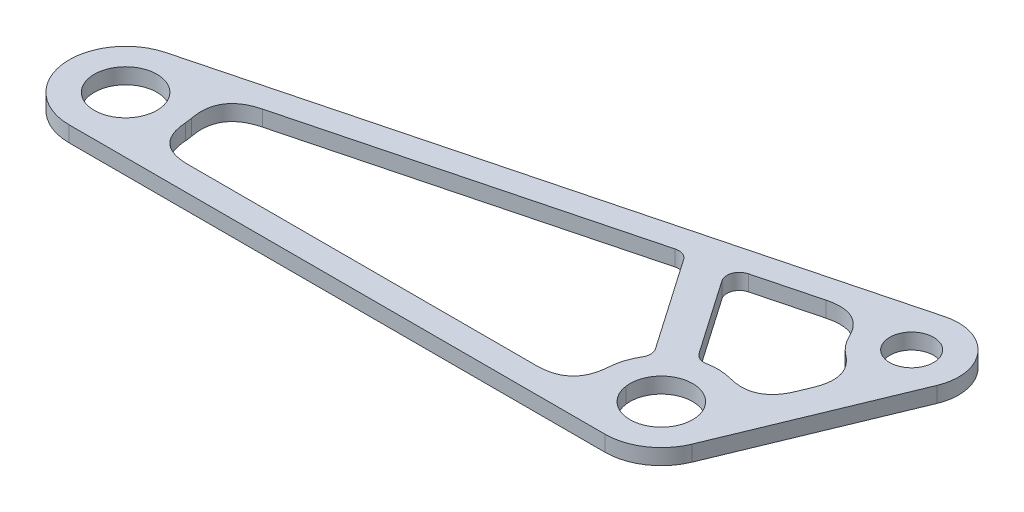
SolidWorks part; units mm, degrees
material "6061-T6 (SS)"
ref_plane "Front Plane" through (0, 0, 0) normal (0, 0, 1) x (1, 0, 0)
ref_plane "Top Plane" through (0, 0, 0) normal (0, 1, 0) x (1, 0, 0)
ref_plane "Right Plane" through (0, 0, 0) normal (1, 0, 0) x (0, 0, -1)
sketch "Sketch1" plane through (0, 0, 0) normal (0, 1, 0) x (1, 0, 0)
  line L0 (0, 0) -> (124.8778, 34.4406) construction
  line L1 (124.8778, 34.4406) -> (108.585, 0) construction
  line L2 (108.585, 0) -> (0, 0) construction
  line L3 (-2.8765, 11.0621) -> (122.4807, 43.6591)
  line L4 (0, -11.43) -> (108.585, -11.43)
  line L5 (119.1487, -4.3651) -> (133.6808, 30.803)
  line L6 (108.585, 0) -> (110.156, -11.3215) construction
  line L7 (-1.5981, 6.1456) -> (123.7591, 38.7426)
  line L8 (114.4537, -2.4251) -> (128.9859, 32.7431)
  line L9 (108.585, -6.35) -> (0, -6.35)
  line L10 (108.585, 0) -> (88.1781, 29.4903) construction
  line L11 (108.585, 0) -> (108.585, 29.9472) construction
  line L12 (61.0805, 22.4441) -> (40.5994, -6.35) construction
  line L13 (65.861, 23.6872) -> (44.4957, -6.35)
  line L14 (56.3001, 21.201) -> (36.7032, -6.35)
  line L15 (84.9059, 28.6395) -> (99.7261, 7.2225)
  line L16 (91.4504, 30.3412) -> (104.9478, 10.8359)
  line L17 (50.84, 8.047) -> (48.2527, 9.8873) construction
  line L18 (50.84, 8.047) -> (53.4272, 6.2067) construction
  line L19 (98.3816, 14.7452) -> (95.7707, 12.9385) construction
  line L20 (98.3816, 14.7452) -> (100.9924, 16.5518) construction
  line L21 (117.1902, 7.5229) -> (124.3826, 24.9285)
  circle A0 centre (0, 0) radius 6.35
  circle A1 centre (124.8778, 34.4406) radius 4.445
  circle A2 centre (108.585, 0) radius 6.35
  circle A3 centre (0, 0) radius 11.43
  circle A4 centre (108.585, 0) radius 11.43
  circle A5 centre (124.8778, 34.4406) radius 9.525
  arc A6 (-2.8765, 11.0621) -> (0, -11.43) centre (0, 0) ccw
  arc A7 (119.1487, -4.3651) -> (108.585, -11.43) centre (108.585, 0) cw
  arc A8 (122.4807, 43.6591) -> (133.6808, 30.803) centre (124.8778, 34.4406) cw
  point P44 (0, 0)
  dimension "D4" = 12.7
  dimension "D5" = 12.7
  dimension "D6" = 8.89
  dimension "D7" = 5.08
  dimension "D8" = 5.08
  dimension "D9" = 5.08
  dimension "D1" = 129.54
  dimension "D2" = 38.1
  dimension "D3" = 108.585
  dimension "D10" = 97.9
  dimension "D11" = 60
  dimension "D12" = 40
  dimension "D13" = 6.35
  dimension "D14" = 1.27
extrude "Boss-Extrude4" add sketch "Sketch1" against normal blind 3.175 contours L9 A3 L7 A0 | A3 L9 A0 L7 | A4 L9 A3 L4 | A5 L3 A3 L7 | A4 L16 L7 L15 | L8 A4 L9 A2 | A4 L8 A2 L9 | A5 L8 A4 L5 | A5 L8 A1 L7 | L8 A5 L7 A1 | A5 L21 A4 L8 region at (2.6053, 0, -10.8105) region at (60.7528, 0, -25.0348) region at (130.5406, 0, -41.7643) region at (54.2925, 0, 8.9551) region at (7.4465, 0, -0.9523) region at (120.7114, 0, -30.8109) region at (112.2307, 0, 5.4512) region at (124.4009, 0, -14.3957) region at (95.1257, 0, -19.3623) region at (121.3624, 0, -15.9386) region at (97.4422, 0, -0.5295)
ref_plane "Plane1" through (108.585, 0, 0) normal (0.1374, 0, 0.9905) x (0.9905, 0, -0.1374)
split line "Split Line1"
sketch "Sketch2" [suppressed] plane through (0, -3.175, 0) normal (0, -1, 0) x (1, 0, 0)
  line L1 (69.4473, -23.6659) -> (60.7288, -1.2641)
  line L2 (62.8949, 2.1892) -> (101.6127, 5.2609)
  line L3 (101.2476, -37.8411) -> (79.7056, -31.0891)
  line L4 (79.2148, -26.4545) -> (98.3531, -15.6299)
  line L5 (59.9072, -25.992) -> (7.538, -8.592)
  line L6 (63.0965, -22.7173) -> (54.4829, 1.0899)
  line L7 (51.7805, 2.7463) -> (11.1946, -2.3078)
  line L8 (73.1912, -24.8791) -> (102.155, -6.1958)
  line L9 (104.5239, -35.0732) -> (102.1201, -17.4966)
  circle A0 centre (111.76, 0) radius 11.43 construction
  circle A3 centre (0, 0) radius 11.43 construction
  arc A4 (11.1946, -2.3078) -> (7.538, -8.592) centre (0, 0) cw
  arc A5 (101.6127, 5.2609) -> (102.155, -6.1958) centre (111.76, 0) ccw
  arc A6 (101.2476, -37.8411) -> (104.5239, -35.0732) centre (102.0073, -35.4173) ccw
  arc A7 (98.3531, -15.6299) -> (102.1201, -17.4966) centre (99.6035, -17.8407) cw
  arc A8 (69.4473, -23.6659) -> (73.1912, -24.8791) centre (71.8144, -22.7446) ccw
  arc A9 (60.7288, -1.2641) -> (62.8949, 2.1892) centre (63.0958, -0.3428) cw
  arc A10 (63.0965, -22.7173) -> (59.9072, -25.992) centre (60.7081, -23.5815) cw
  arc A11 (54.4829, 1.0899) -> (51.7805, 2.7463) centre (52.0944, 0.2257) ccw
  arc A12 (79.2148, -26.4545) -> (79.7056, -31.0891) centre (80.4653, -28.6654) ccw
  dimension "D1" = 2.54
  dimension "D2" = 2.54
  dimension "D3" = 2.54
  dimension "D4" = 2.54
  dimension "D5" = 2.54
  dimension "D6" = 2.54
  dimension "D7" = 2.54
extrude "Cut-Extrude2" [suppressed] cut sketch "Sketch2" against normal through all
fillet "Fillet1" radius 7.62 6 edges at (99.0812, -1.5875, 6.35) (115.606, -1.5875, -36.6225) (9.5038, -1.5875, 6.35) (7.5999, -1.5875, -8.5374) (117.1902, -1.5875, -7.5229) (124.3826, -1.5875, -24.9285) conic rho 0.5
fillet "Fillet2" radius 2.54 4 edges at (91.4504, -1.5875, -30.3412) (104.9478, -1.5875, -10.8359) (99.7261, -1.5875, -7.2225) (84.9059, -1.5875, -28.6395)
equation "\"x\"= .05"
